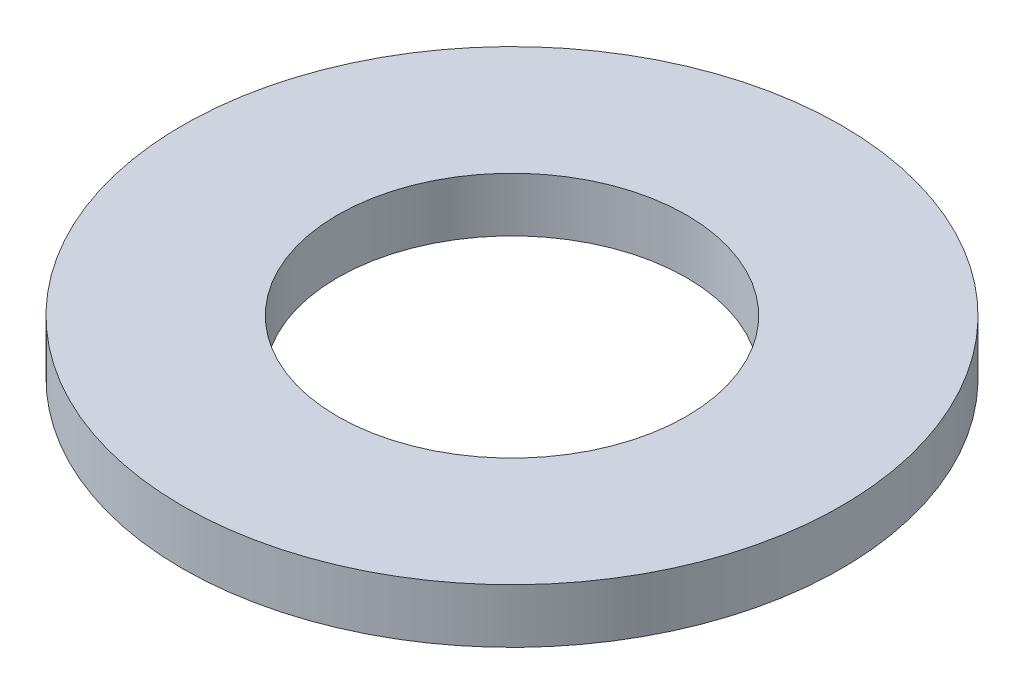
SolidWorks part; units mm, degrees
ref_plane "Front Plane" through (0, 0, 0) normal (0, 0, 1) x (1, 0, 0)
ref_plane "Top Plane" through (0, 0, 0) normal (0, 1, 0) x (1, 0, 0)
ref_plane "Right Plane" through (0, 0, 0) normal (1, 0, 0) x (0, 0, -1)
sketch "Sketch1" plane through (0, 0, 0) normal (0, 1, 0) x (1, 0, 0)
  circle A0 centre (0, 0) radius 85
  dimension "FLANGE_OD" = 170
extrude "Boss-Extrude1" add sketch "Sketch1" along normal blind 14
sketch "Sketch2" plane through (0, 0, 0) normal (0, 1, 0) x (1, 0, 0)
  circle A0 centre (0, 0) radius 45
  dimension "BORE_D" = 90
extrude "Cut-Extrude1" cut sketch "Sketch2" along normal through all
sketch "Sketch3" plane through (0, 14, 0) normal (0, 1, 0) x (1, 0, 0)
  circle A0 centre (0, 0) radius 26.571 construction
  circle A1 centre (-26.571, 0) radius 6.6867
  dimension "BOLT_D" = 13.3735
  dimension "BOLT_PCD" = 53.1419
extrude "Cut-Extrude2" cut sketch "Sketch3" against normal blind 10.2281 rebuild error yes
pattern_circular "CirPattern1" count 5 over 360 rebuild error yes
